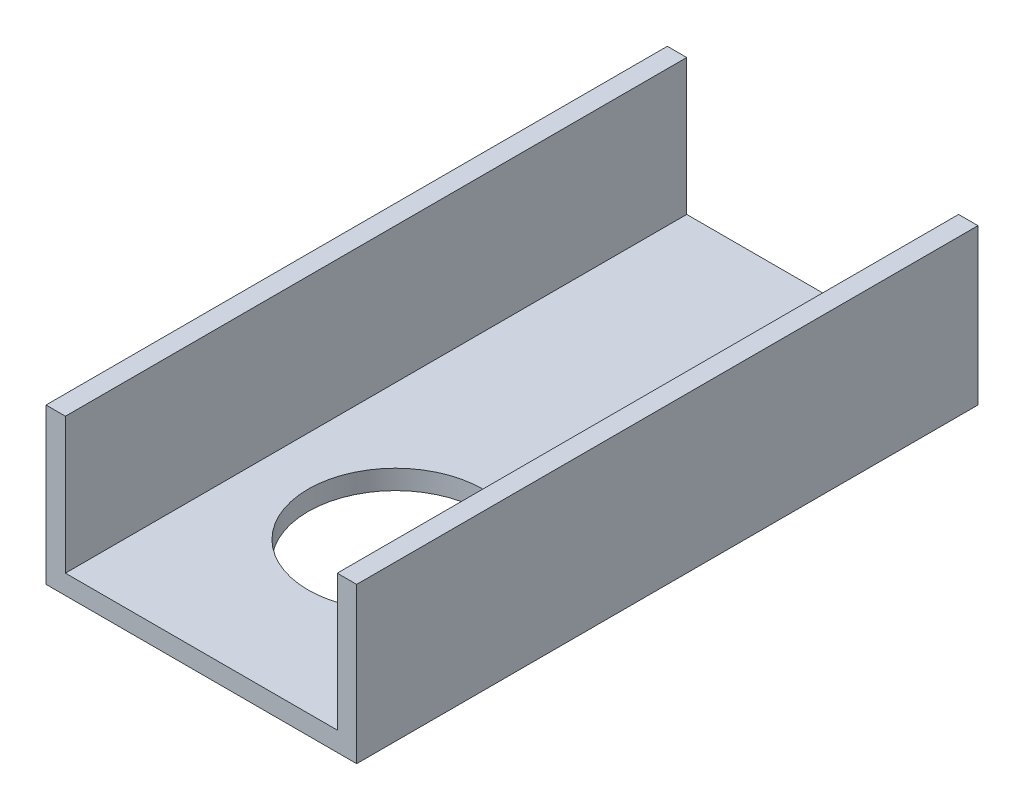
SolidWorks part; units mm, degrees
material "6063-T6"
ref_plane "Front" through (0, 0, 0) normal (0, 0, 1) x (1, 0, 0)
ref_plane "Top" through (0, 0, 0) normal (0, 1, 0) x (1, 0, 0)
ref_plane "Right" through (0, 0, 0) normal (1, 0, 0) x (0, 0, -1)
sketch "Sketch1" plane through (0, 0, 0) normal (0, 0, 1) x (1, 0, 0)
  line L0 (47.625, 3.175) -> (47.625, 25.4)
  line L1 (0, 0) -> (50.8, 0)
  line L2 (0, 0) -> (0, 25.4)
  line L4 (50.8, 0) -> (50.8, 25.4)
  line L5 (3.175, 3.175) -> (47.625, 3.175)
  line L6 (3.175, 3.175) -> (3.175, 25.4)
  line L7 (50.8, 25.4) -> (47.625, 25.4)
  line L8 (0, 25.4) -> (3.175, 25.4)
  dimension "D1" = 25.4
  dimension "D2" = 50.8
  dimension "D3" = 3.175
extrude "Boss-Extrude1" add sketch "Sketch1" along normal blind 101.6
sketch "Sketch2" plane through (0, 0, 0) normal (0, -1, 0) x (1, 0, 0)
  line L0 (25.4, 69.85) -> (25.4, 101.6) construction
  line L1 (0, 101.6) -> (50.8, 101.6) construction
  circle A0 centre (25.4, 69.85) radius 14.2875
  dimension "D1" = 28.575
  dimension "D2" = 31.75
extrude "Cut-Extrude1" cut sketch "Sketch2" against normal up to next
sketch "Sketch3" plane through (0, 3.175, 0) normal (0, 1, 0) x (1, 0, 0)
  line L1 (44.45, -22.225) -> (47.625, -22.225)
  line L2 (44.45, -22.225) -> (44.45, 0)
  line L3 (44.45, 0) -> (47.625, 0)
  line L4 (47.625, -22.225) -> (47.625, 0)
  line L5 (44.45, -22.225) -> (47.625, 0) construction
  line L6 (44.45, 0) -> (47.625, -22.225) construction
  line L8 (47.625, -101.6) -> (47.625, 0) construction
  line L9 (47.625, 0) -> (3.175, 0) construction
  point P4 (46.0375, -11.1125)
  dimension "D1" = 22.225
  dimension "D2" = 3.175
extrude "Cut-Extrude2" cut sketch "Sketch3" against normal up to next
